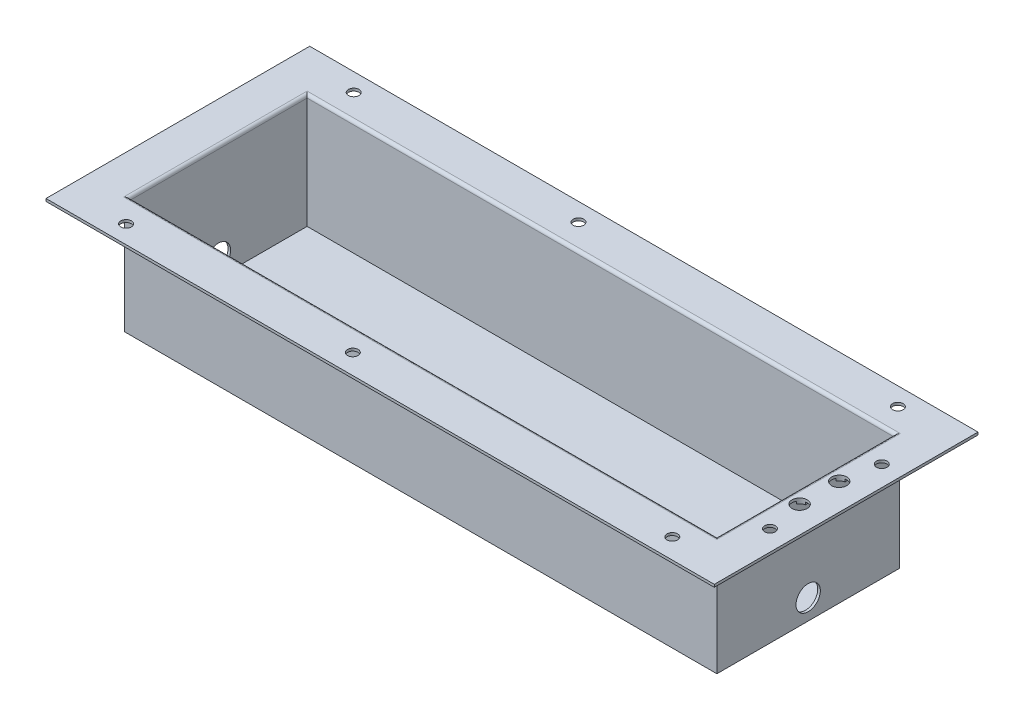
SolidWorks part; units mm, degrees
material "5052-H32"
ref_plane "Front Plane" through (0, 0, 0) normal (0, 0, 1) x (1, 0, 0)
ref_plane "Top Plane" through (0, 0, 0) normal (0, 1, 0) x (1, 0, 0)
ref_plane "Right Plane" through (0, 0, 0) normal (1, 0, 0) x (0, 0, -1)
sketch "Sketch1" plane through (0, 0, 0) normal (0, 1, 0) x (1, 0, 0)
  line L1 (185.42, 57.15) -> (-185.42, 57.15)
  line L2 (185.42, 57.15) -> (185.42, -57.15)
  line L3 (185.42, -57.15) -> (-185.42, -57.15)
  line L4 (-185.42, 57.15) -> (-185.42, -57.15)
  line L5 (185.42, 57.15) -> (-185.42, -57.15) construction
  line L6 (185.42, -57.15) -> (-185.42, 57.15) construction
  point P0 (0, 0)
  dimension "D1" = 114.3
  dimension "D2" = 370.84
extrude "Boss-Extrude1" add sketch "Sketch1" along normal blind 1.6256
sketch "Sketch2" plane through (0, 1.6256, 0) normal (0, 1, 0) x (1, 0, 0)
  line L0 (-185.42, -57.15) -> (-183.7944, -57.15) construction
  line L1 (-185.42, -57.15) -> (185.42, -57.15) construction
  line L3 (185.42, 57.15) -> (-185.42, 57.15) construction
  line L4 (185.42, -57.15) -> (185.42, -55.5244) construction
  line L5 (185.42, -57.15) -> (185.42, 57.15) construction
  line L6 (183.7944, 55.5244) -> (-183.7944, 55.5244)
  line L7 (-185.42, 57.15) -> (-183.7944, 57.15)
  line L8 (183.7944, 55.5244) -> (183.7944, -55.5244)
  line L9 (185.42, -57.15) -> (-185.42, -57.15)
  line L10 (185.42, -57.15) -> (185.42, 57.15)
  line L11 (185.42, 57.15) -> (-185.42, 57.15)
  line L12 (-185.42, -57.15) -> (-185.42, 57.15)
  line L13 (185.42, -57.15) -> (-185.42, 57.15) construction
  line L14 (185.42, 57.15) -> (-185.42, -57.15) construction
  line L15 (183.7944, -55.5244) -> (-183.7944, -55.5244)
  line L16 (-183.7944, 55.5244) -> (-183.7944, -55.5244)
  line L17 (183.7944, 55.5244) -> (-183.7944, -55.5244) construction
  line L18 (183.7944, -55.5244) -> (-183.7944, 55.5244) construction
  point P15 (0, 0)
  point P17 (0, 0)
  line M7 (-185.42, 57.15) -> (-185.42, -57.15)
  line M8 (-185.42, -57.15) -> (185.42, -57.15)
  line M9 (185.42, -57.15) -> (185.42, 57.15)
  line M10 (185.42, 57.15) -> (-185.42, 57.15)
  dimension "D1" = 1.6256
  dimension "D2" = 1.6256
extrude "Boss-Extrude2" add sketch "Sketch2" along normal blind 69.85 contours L16 L6 L8 L15 M10 M7 M8 M9 region at (-184.6072, 1.6256, -53.2694)
sketch "Sketch3" plane through (0, 71.4756, 0) normal (0, 1, 0) x (1, 0, 0)
  line L0 (185.42, 57.15) -> (-185.42, 57.15) construction
  line L1 (183.7944, 55.5244) -> (-183.7944, 55.5244)
  line L2 (183.7944, 55.5244) -> (183.7944, -55.5244)
  line L3 (183.7944, -55.5244) -> (-183.7944, -55.5244)
  line L4 (-183.7944, 55.5244) -> (-183.7944, -55.5244)
  line L5 (183.7944, 55.5244) -> (-183.7944, -55.5244) construction
  line L6 (183.7944, -55.5244) -> (-183.7944, 55.5244) construction
  line L7 (209.1944, 82.55) -> (-209.1944, 82.55)
  line L8 (209.1944, 82.55) -> (209.1944, -82.55)
  line L9 (209.1944, -82.55) -> (-209.1944, -82.55)
  line L10 (-209.1944, 82.55) -> (-209.1944, -82.55)
  line L11 (209.1944, 82.55) -> (-209.1944, -82.55) construction
  line L12 (209.1944, -82.55) -> (-209.1944, 82.55) construction
  point P0 (0, 0)
  point P7 (0, 0)
  dimension "D1" = 25.4
  dimension "D2" = 25.4
extrude "Boss-Extrude3" add sketch "Sketch3" along normal blind 1.6256
fillet "Fillet1" radius 1.905 8 edges at (0, 71.4756, 57.15) (185.42, 71.4756, 0) (0, 71.4756, -57.15) (-185.42, 71.4756, 0) (-183.7944, 73.1012, 0) (0, 73.1012, -55.5244) (183.7944, 73.1012, 0) (0, 73.1012, 55.5244)
sketch "Sketch6" plane through (0, 73.1012, 0) normal (0, 1, 0) x (1, 0, 0)
  line L0 (185.6994, -57.4294) -> (-185.6994, -57.4294) construction
  line L1 (188.2394, -59.9694) -> (-188.2394, -59.9694)
  line L3 (188.2394, -63.1444) -> (-188.2394, -63.1444)
  line L5 (188.2394, -59.9694) -> (-188.2394, -63.1444) construction
  line L6 (188.2394, -63.1444) -> (-188.2394, -59.9694) construction
  line L8 (0, 0) -> (-45.7363, 0) construction
  line L9 (-191.4144, 63.1444) -> (-188.2394, 63.1444)
  line L10 (-191.4144, 63.1444) -> (-191.4144, -63.1444)
  line L11 (-191.4144, -63.1444) -> (-188.2394, -63.1444)
  line L12 (-188.2394, 59.9694) -> (-188.2394, -59.9694)
  line L13 (-191.4144, 63.1444) -> (-189.8269, 0) construction
  line L14 (-191.4144, -63.1444) -> (-189.8269, 0) construction
  line L15 (-45.7363, 0) -> (27.0509, 0) construction
  line L18 (188.2394, 63.1444) -> (-188.2394, 63.1444)
  line L19 (188.2394, 59.9694) -> (-188.2394, 59.9694)
  line L20 (185.6994, 57.4294) -> (185.6994, -57.4294) construction
  line L21 (191.4144, 63.1444) -> (188.2394, 63.1444)
  line L22 (191.4144, 63.1444) -> (191.4144, -63.1444)
  line L23 (191.4144, -63.1444) -> (188.2394, -63.1444)
  line L24 (188.2394, 59.9694) -> (188.2394, -59.9694)
  line L25 (191.4144, 63.1444) -> (189.8269, 0) construction
  line L26 (191.4144, -63.1444) -> (189.8269, 0) construction
  point P0 (0, -61.5569)
  point P9 (-189.8269, 0)
  point P23 (189.8269, 0)
  dimension "D1" = 3.175
  dimension "D2" = 2.54
  dimension "D3" = 3.175
  dimension "D6" = 3.175
  dimension "D7" = 2.54
extrude "Boss-Extrude4" add sketch "Sketch6" against normal blind 3.175 contours L3 L11 L10 L9 L18 L21 L22 L23 | L1 L12 L19 L24
sketch "Sketch8" plane through (185.42, 0, 0) normal (1, 0, 0) x (0, 0, -1)
  line L0 (0, 0) -> (0, 12.7) construction
  line L1 (0, 55) -> (0, -55) construction
  circle A0 centre (0, 12.7) radius 7.62
  dimension "D1" = 15.24
extrude "Cut-Extrude2" cut sketch "Sketch8" against normal through all
sketch "Sketch13" plane through (0, 73.1012, 0) normal (0, 1, 0) x (1, 0, 0)
  line L2 (-209.1944, 0) -> (213.4231, 0) construction
  line L5 (-209.1944, -82.55) -> (209.1944, -82.55) construction
  line L6 (209.1944, -82.55) -> (209.1944, 82.55) construction
  line L8 (-191.4144, -63.1444) -> (191.4144, -63.1444) construction
  line L9 (0, 63.1444) -> (0, -59.9694) construction
  line L10 (-191.4144, 63.1444) -> (191.4144, 63.1444) construction
  line L11 (188.2394, -59.9694) -> (-188.2394, -59.9694) construction
  circle A0 centre (-29.6556, -70) radius 3.325
  circle A1 centre (170.3444, -70) radius 3.325
  circle A2 centre (170.3444, 71.2567) radius 3.325
  circle A3 centre (-29.6556, 71.2567) radius 3.325
  circle A4 centre (196.4944, -35) radius 3.325
  circle A9 centre (196.4944, 35) radius 3.325
  circle A10 centre (-170.3444, 71.2567) radius 3.325
  circle A11 centre (-170.3444, -71.2567) radius 3.325
  dimension "D3" = 38.85
  dimension "D4" = 12.55
  dimension "D5" = 47.55
  dimension "D6" = 12.7
  dimension "D7" = 6.65
  dimension "D8" = 6.65
  dimension "D1" = 12.55
  dimension "D2" = 238.85
  dimension "D9" = 63.1444
  dimension "D10" = 134.4011
  dimension "D11" = 422.6175
  dimension "D12" = 209.1944
extrude "Cut-Extrude10" cut sketch "Sketch13" against normal through all both
sketch "Sketch14" plane through (0, 73.1012, 0) normal (0, 1, 0) x (1, 0, 0)
  line L0 (-209.1944, 0) -> (192.4459, 0) construction
  line L2 (209.1944, -82.55) -> (209.1944, -8.9114) construction
  circle A0 centre (192.4459, -12.3885) radius 4.75
  circle A2 centre (192.4459, 12.3885) radius 4.75
  circle A3 centre (-29.6556, -70) radius 3.325 construction
  dimension "D2" = 401.6403
  dimension "D3" = 9.5
  dimension "D1" = 70.1615
  dimension "D4" = 222.1015
  dimension "D5" = 238.85
  dimension "D6" = 57.6115
  dimension "D7" = 70
  dimension "D8" = 73.6386
extrude "Cut-Extrude11" cut sketch "Sketch14" against normal through all both
